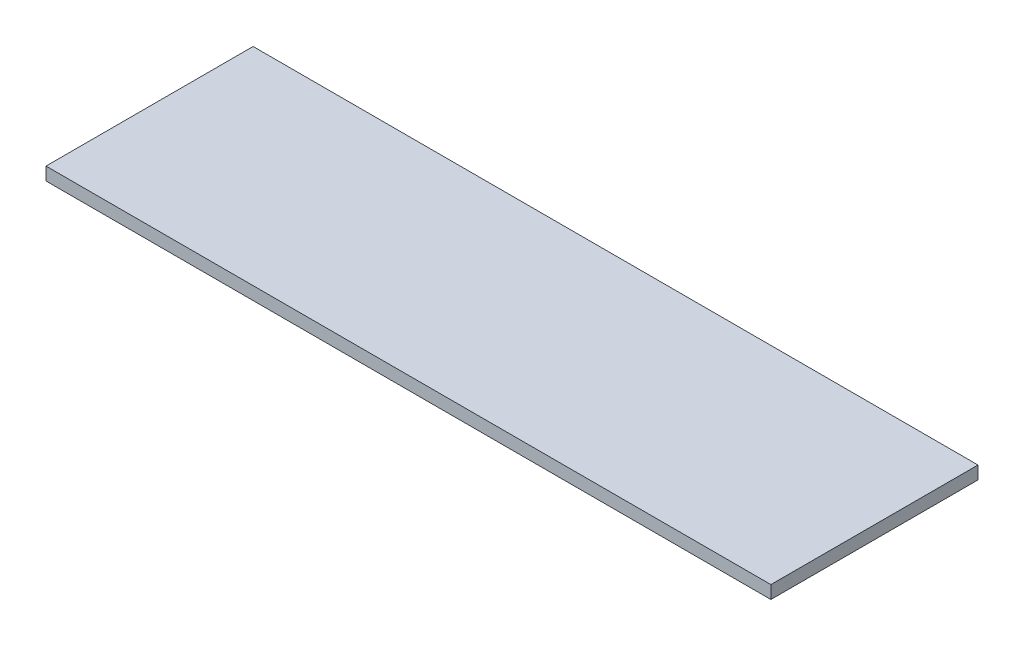
SolidWorks part; units mm, degrees
ref_plane "Front Plane" through (0, 0, 0) normal (0, 0, 1) x (1, 0, 0)
ref_plane "Top Plane" through (0, 0, 0) normal (0, 1, 0) x (1, 0, 0)
ref_plane "Right Plane" through (0, 0, 0) normal (1, 0, 0) x (0, 0, -1)
sketch "Sketch1" plane through (0, 0, 0) normal (0, 1, 0) x (1, 0, 0)
  line L1 (-28, -8) -> (28, -8)
  line L2 (-28, -8) -> (-28, 8)
  line L3 (-28, 8) -> (28, 8)
  line L4 (28, -8) -> (28, 8)
  line L5 (-28, -8) -> (28, 8) construction
  line L6 (-28, 8) -> (28, -8) construction
  point P0 (0, 0)
  dimension "D1" = 56
  dimension "D2" = 16
extrude "Boss-Extrude1" add sketch "Sketch1" along normal blind 1
